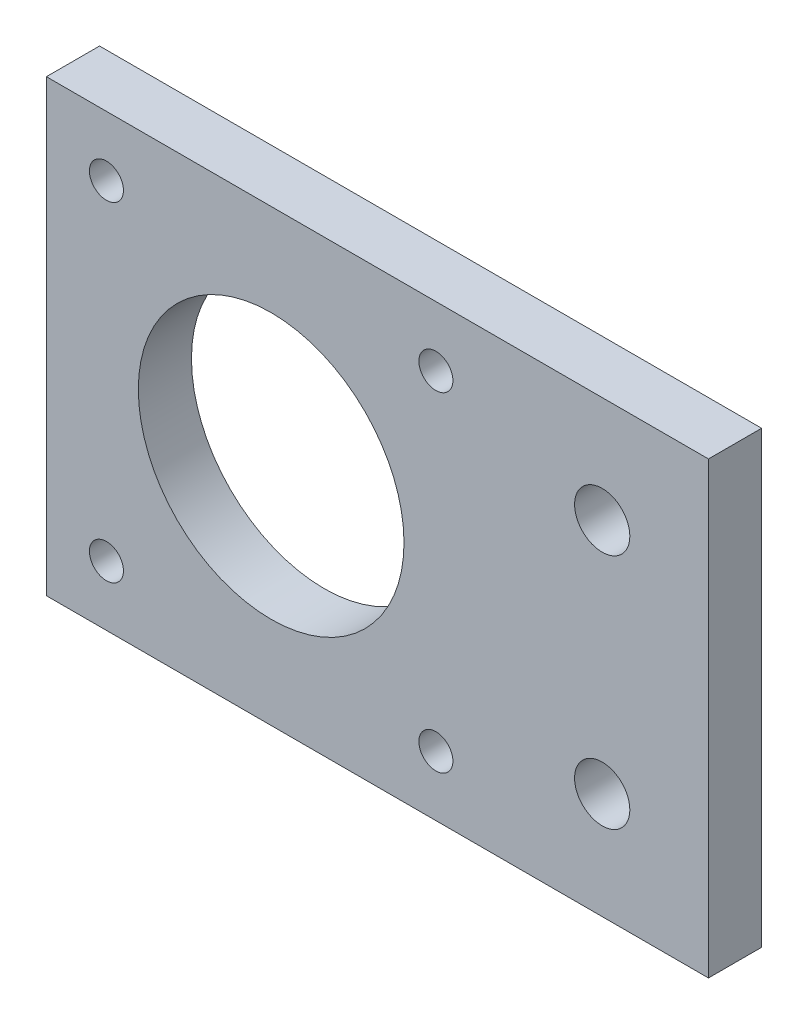
SolidWorks part; units mm, degrees
material "PET"
ref_plane "Front Plane" through (0, 0, 0) normal (0, 0, 1) x (1, 0, 0)
ref_plane "Top Plane" through (0, 0, 0) normal (0, 1, 0) x (1, 0, 0)
ref_plane "Right Plane" through (0, 0, 0) normal (1, 0, 0) x (0, 0, -1)
sketch "Sketch2" plane through (0, 0, 0) normal (0, 0, 1) x (1, 0, 0)
  line L0 (-21.15, 21.15) -> (21.15, -21.15) construction
  line L1 (-21.15, 21.15) -> (21.15, 21.15)
  line L2 (-21.15, 21.15) -> (-21.15, -21.15)
  line L3 (-21.15, -21.15) -> (21.15, -21.15)
  line L4 (21.15, 21.15) -> (21.15, -21.15)
  line L5 (21.15, 21.15) -> (41.15, 21.15)
  line L6 (21.15, 21.15) -> (21.15, -21.15)
  line L7 (21.15, -21.15) -> (41.15, -21.15)
  line L8 (41.15, 21.15) -> (41.15, -21.15)
  line L9 (31.15, 21.15) -> (31.15, -21.15) construction
  line L10 (-15.5, -15.5) -> (15.5, 15.5) construction
  circle A0 centre (31.15, 11.15) radius 2.6
  circle A1 centre (31.15, -11.15) radius 2.6
  circle A2 centre (-15.5, 15.5) radius 1.6
  circle A3 centre (15.5, -15.5) radius 1.6
  circle A4 centre (15.5, 15.5) radius 1.6
  circle A5 centre (-15.5, -15.5) radius 1.6
  dimension "D4" = 5.2
  dimension "D5" = 5.2
  dimension "D8" = 3.2
  dimension "D9" = 3.2
  dimension "D10" = 3.2
  dimension "D11" = 3.2
  dimension "D1" = 20
  dimension "D2" = 42.3
  dimension "D3" = 42.3
  dimension "D6" = 10
  dimension "D7" = 10
  dimension "D12" = 31
  dimension "D13" = 31
extrude "Boss-Extrude1" add sketch "Sketch2" along normal blind 5 contours L4 L1 L2 L3 A5 A4 A3 A2 | L8 L5 L4 L7 A1 A0 region at (0, 0, 0) region at (31.15, 0, 0)
sketch "Sketch3" plane through (0, 0, 0) normal (0, 0, -1) x (-1, 0, 0)
  circle A0 centre (0, 0) radius 12.5
  dimension "D1" = 25
extrude "Cut-Extrude1" cut sketch "Sketch3" against normal blind 10
